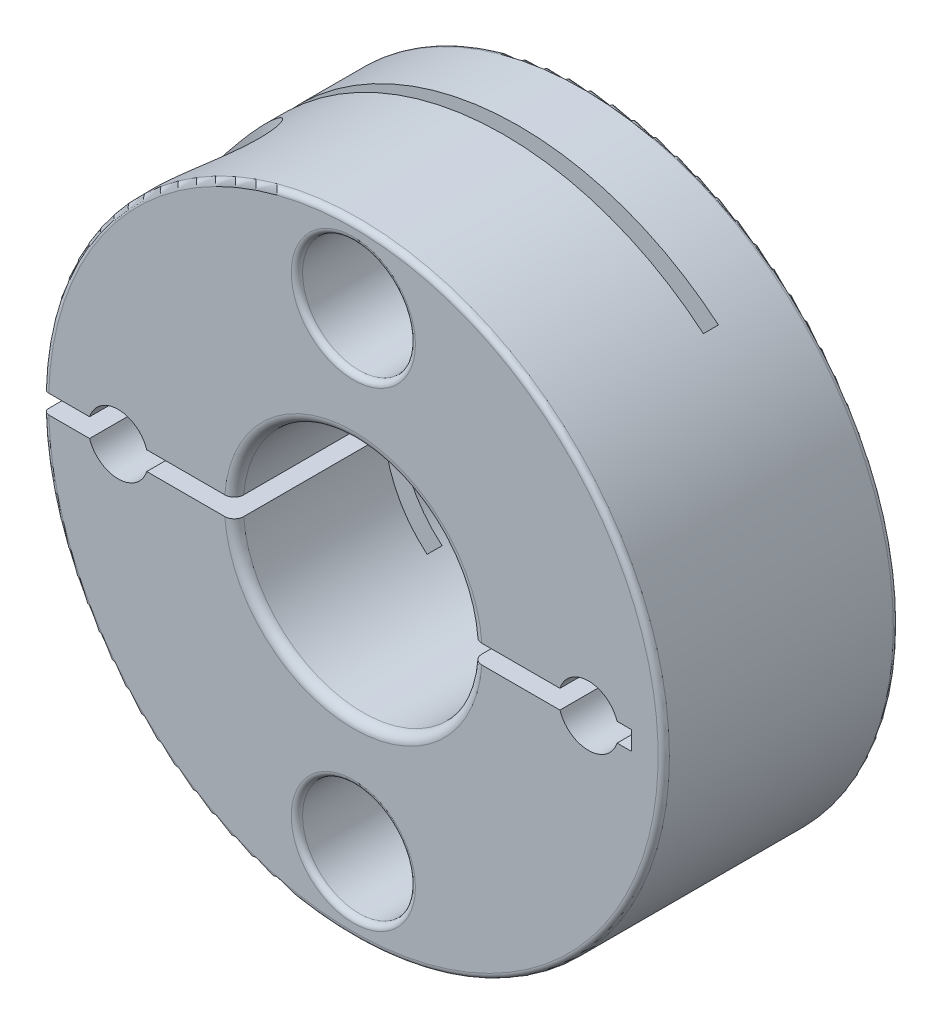
SolidWorks part; units mm, degrees
ref_plane "Front Plane" through (0, 0, 0) normal (0, 0, 1) x (1, 0, 0)
ref_plane "Top Plane" through (0, 0, 0) normal (0, 1, 0) x (1, 0, 0)
ref_plane "Right Plane" through (0, 0, 0) normal (1, 0, 0) x (0, 0, -1)
ref_axis "Axis_X" through (-6.6084, 0, 0) along (1, 0, 0)
ref_axis "Axis_Y" through (0, 6.6, 0) along (0, -1, 0)
ref_axis "Axis_Z" through (0, 0, -0.3894) along (0, 0, 1)
ref_plane "Dim.MSM_9" through (0, 0, 6) normal (0, 0, 1) x (1, 0, 0)
ref_plane "Dim.A" through (0, 0, 12) normal (0, 0, 1) x (1, 0, 0)
ref_plane "Dim.MSM_13" through (0, 0, 4) normal (0, 0, 1) x (1, 0, 0)
ref_plane "Dim.B_s_1" through (0, 0, 2) normal (0, 0, 1) x (1, 0, 0)
sketch "Sketch1" plane through (0, 0, 0) normal (0, 0, 1) x (1, 0, 0)
  circle A0 centre (0, 0) radius 16.5
  dimension "D" = 33
extrude "Boss-Extrude1" add sketch "Sketch1" along normal blind 12.5
ref_plane "Plane1" through (0, 0, 3.7) normal (0, 0, -1) x (-1, 0, 0)
sketch "Sketch2" plane through (0, 0, 3.7) normal (0, 0, -1) x (-1, 0, 0)
  line L0 (-10.606, 12.6397) -> (10.606, -12.6397)
  line L1 (0, 0) -> (0, 16.5) construction
  arc A0 (10.606, -12.6397) -> (-10.606, 12.6397) centre (0, 0) ccw
  dimension "D" = 33
  dimension "FIX_1" = 40
extrude "Cut-Extrude21" cut sketch "Sketch2" against normal blind 0.8
sketch "Sketch15" plane through (0, 0, 3.7) normal (0, 0, -1) x (-1, 0, 0)
  arc A0 (13.377, -9.6595) -> (1.1998, 16.4563) centre (0, 0) ccw
  arc A1 (1.1998, 16.4563) -> (13.377, -9.6595) centre (13.595, 6.339) ccw
  dimension "D" = 33
  dimension "MSM_63" = 16
  dimension "MSM_62" = 13.595
  dimension "MSM_61" = 6.339
extrude "Cut-Extrude22" [suppressed] cut sketch "Sketch15" against normal blind 0.8
sketch "Sketch4" plane through (0, 0, 12.5) normal (0, 0, 1) x (1, 0, 0)
  circle A0 centre (0, 0) radius 6.35
  dimension "D1_s" = 12.7
extrude "Cut-Extrude2" cut sketch "Sketch4" against normal through all
fillet "Fillet3" radius 0.5 2 edges at (6.35, 0, 0) (6.35, 0, 12.5)
sketch "Sketch3" plane through (0, 0, 0) normal (0, 1, 0) x (1, 0, 0)
  line L0 (0, 0) -> (0, -12.5) construction
  line L1 (-16.5, -12.5) -> (16.5, -12.5) construction
  line L2 (0, -4.5) -> (-16.5, -4.5)
  line L3 (-16.5, -4.5) -> (-16.5, -12.5)
  line L4 (-16.5, -12.5) -> (14.7819, -12.5)
  line L5 (6.6, -3.7) -> (-6.6, -3.7) construction
  line L6 (0, -4.5) -> (0, -7.5002)
  arc A0 (14.7819, -12.5) -> (0, -7.5002) centre (3.924, -20.25) ccw
  dimension "MSM_6" = 13.34
  dimension "D" = 33
  dimension "LF" = 12.5
  dimension "MSM_2" = 0.8
  dimension "MSM_4" = 3.924
  dimension "MSM_5" = 7.75
extrude "Cut-Extrude11" cut sketch "Sketch3" against normal mid plane 1
sketch "Sketch14" plane through (0, 0, 0) normal (0, 1, 0) x (1, 0, 0)
  line L0 (0, 0) -> (0, -12.5) construction
  line L3 (0, -4.5) -> (-16.5, -4.5)
  line L4 (-16.5, -4.5) -> (-16.5, -12.5)
  line L5 (-16.5, -12.5) -> (10.8579, -12.5)
  line L6 (6.6, -3.7) -> (-6.6, -3.7) construction
  line L8 (0, -4.5) -> (0, -6.91)
  arc A0 (10.8579, -12.5) -> (0, -6.91) centre (0, -20.25) ccw
  dimension "MSM_6" = 13.34
  dimension "MSM_2" = 0.8
  dimension "D" = 33
  dimension "LF" = 12.5
  dimension "MSM_5" = 7.75
extrude "Cut-Extrude12" [suppressed] cut sketch "Sketch14" against normal mid plane 1
sketch "Sketch5" plane through (0, 0, 0) normal (0, 0, -1) x (-1, 0, 0)
  circle A0 centre (0, 12.5) radius 3
  circle A1 centre (0, -12.5) radius 3
  circle A2 centre (0, 0) radius 12.5 construction
  dimension "MSM_8" = 25
  dimension "KSS_1" = 6
extrude "Cut-Extrude4" cut sketch "Sketch5" against normal through all
hole_wizard "Tap1" positions "Sketch6" profile "Sketch7" hole size "M1.6x0.35" standard "JIS"
sketch "Sketch6" plane through (0, 0, 0) normal (0, 0, -1) x (-1, 0, 0)
  circle A0 centre (0, 0) radius 12.5 construction
  point P0 (-12.5, 0)
  point P2 (12.5, 0)
  dimension "MSM_8" = 25
sketch "Sketch7" plane through (12.5, 0, 0) normal (1, 0, 0) x (0, 1, 0)
  line L0 (0, 0) -> (0, 4.7388)
  line L1 (0, 4.7388) -> (1.2295, 4)
  line L2 (1.2295, 4) -> (1.2295, 0)
  line L5 (1.2295, 0) -> (0, 0)
  line L10 (0, 4.7388) -> (-1.2295, 4) construction
  line L11 (0, -6.35) -> (0, 107.95) construction
  dimension "HSD_1" = 2.459
  dimension "HSL_1" = 4
  dimension "Drill Angle" = 118
cosmetic thread "Thread1" parameters "MSM_10"=3
cosmetic thread "Thread2" parameters "MSM_10"=3
sketch "Sketch8" plane through (0, 0, 0) normal (0, 0, -1) x (-1, 0, 0)
  circle A0 centre (0, 12.5) radius 3.25
  circle A1 centre (0, -12.5) radius 3.25
  dimension "MSM_11" = 6.5
extrude "Cut-Extrude23" [suppressed] cut sketch "Sketch8" against normal blind 4
ref_plane "Plane2" through (0, 4, 0) normal (0, 1, 0) x (1, 0, 0)
sketch "Sketch9" plane through (0, 4, 0) normal (0, 1, 0) x (1, 0, 0)
  line L2 (-16.4924, -12.5) -> (16.5, -12.5) construction
  circle A0 centre (-12, -8.5) radius 3
  dimension "MSM_14" = 6
  dimension "F" = 4
  dimension "KSS_2" = 12
extrude "Cut-Extrude6" cut sketch "Sketch9" along normal through all
sketch "Sketch11" plane through (0, 4, 0) normal (0, 1, 0) x (1, 0, 0)
  circle A0 centre (-12, -8.5) radius 1.6
  dimension "MSM_15" = 3.2
extrude "Cut-Extrude7" cut sketch "Sketch11" against normal blind 4.5
hole_wizard "Tap2" positions "Sketch12" profile "Sketch13" hole size "M1.6x0.35" standard "JIS" end condition through all
sketch "Sketch12" plane through (0, 0, 0) normal (0, 1, 0) x (1, 0, 0)
  point P0 (-12, -8.5)
sketch "Sketch13" plane through (-12, 0, 8.5) normal (1, 0, 0) x (0, 0, 1)
  line L0 (0, 0) -> (0, 16.5)
  line L1 (0, 16.5) -> (1.2295, 16.5)
  line L2 (1.2295, 16.5) -> (1.2295, 0)
  line L5 (1.2295, 0) -> (0, 0)
  line L11 (0, -6.35) -> (0, 107.95) construction
  dimension "HSD_2" = 2.459
  dimension "Thru Hole Depth" = 16.5
cosmetic thread "Thread3" parameters "MSM_17"=3
fillet "Fillet1" radius 0.3 2 edges at (-3, -12.5, 12.5) (-3, 12.5, 12.5)
fillet "Fillet2" radius 0.3 2 edges at (16.5, 0, 0) (16.5, 0, 12.5)
fillet "Fillet4" radius 0.1 1 edges at (-12, 4, 10.1)
ref_plane "Plane3" through (0, 0, 4) normal (0, 0, 1) x (1, 0, 0)
sketch "Sketch16" plane through (0, 0, 4) normal (0, 0, -1) x (-1, 0, 0)
  circle A0 centre (12.5, 0) radius 1.6
  circle A1 centre (-12.5, 0) radius 1.6
  dimension "MSM_64" = 3.2
extrude "Cut-Extrude24" cut sketch "Sketch16" against normal through all
sketch "Sketch18" plane through (0, 0, 0) normal (0, 0, 1) x (1, 0, 0)
  line L0 (-4.8, 0) -> (0, 0) construction
  circle A0 centre (0, 12.5) radius 2.4
  circle A1 centre (0, -12.5) radius 2.4
  dimension "FIX_91" = 4.8
  dimension "MSM_8" = 25
  dimension "FIX_92" = 4.8
extrude "Cut-Extrude25" [suppressed] cut sketch "Sketch18" along normal blind 5
sketch "Sketch17" [suppressed] plane through (0, 0, 0) normal (0, 0, 1) x (1, 0, 0)
  line L0 (0, 1.5) -> (0, 0) construction
  line L1 (0, 0) -> (1.7678, -1.7678) construction
  line L2 (0.0835, -1.4977) -> (1.0607, -2.4749)
  line L3 (1.0607, -2.4749) -> (2.4749, -1.0607)
  line L4 (2.4749, -1.0607) -> (1.4977, -0.0835)
  arc A0 (1.4977, -0.0835) -> (0.0835, -1.4977) centre (0, 0) ccw
  dimension "D1_s" = 12.7
  dimension "FIX_2" = 135
  dimension "B_s_1" = 2
  dimension "T_s_1" = 1
extrude "Cut-Extrude1" [suppressed] cut sketch "Sketch17" along normal through all
equation "\"Factor\"= 1.082532"
equation "\"KSS_1\"= IIF ( ( \"D\" = 26 and \"D1_s\" = 14 ) , 3 , \"MSM_9\" )"
equation "\"KSS_2\"= IIF ( ( \"D\" = 26 and \"D1_s\" = 14 ) , 9 , \"A\" )"
equation "\"KSS_3\"= IIF ( ( \"D\" = 26 and \"D1_s\" = 14 ) , 4 , IIF ( ( \"D\" = 26 and \"D1_s\" = 13 ) , 4 , \"MSM_13\" ) )"
equation "\"Cut-Extrude25\"= IIF ( ( \"D\" = 26 and \"D1_s\" = 14 ) , \"unsuppressed\" , \"suppressed\" )"
equation "\"T_s_1\"= IIF ( \"B_s_1\" = 12 , 3.3 , IIF ( \"B_s_1\" = 10 , 3.3 , IIF ( \"B_s_1\" = 8 , 3.3 , IIF ( \"B_s_1\" = 6 , 2.8 , IIF ( \"B_s_1\" = 5 , 2.3 , IIF ( \"B_s_1\" = 4 , 1.8 , IIF ( \"B_s_1\" = 3 , 1.4 , IIF ( \"B_s_1\" = 2 , 1 , 1 ) ) ) ) ) ) ) )"
